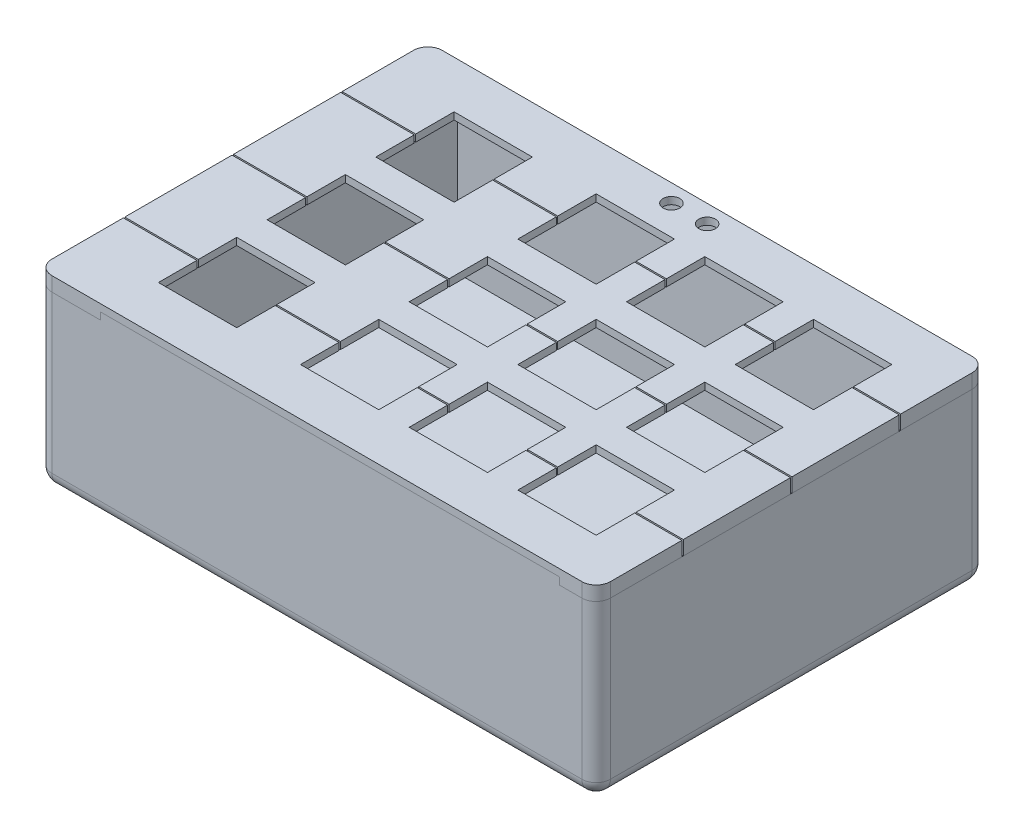
SolidWorks part; units mm, degrees
other "Lid4"
other "Lid2"
other "Lid3"
other "Lid1"
other "Base"
ref_plane "Front" through (0, 0, 0) normal (0, 0, 1) x (1, 0, 0)
ref_plane "Top" through (0, 0, 0) normal (0, 1, 0) x (1, 0, 0)
ref_plane "Right" through (0, 0, 0) normal (1, 0, 0) x (0, 0, -1)
sketch "Sketch1" plane through (0, 0, 0) normal (0, 1, 0) x (1, 0, 0)
  line L0 (2.6035, 12.3825) -> (8.0137, 12.3825) construction
  line L1 (-49.7332, -34.7472) -> (49.7332, -34.7472)
  line L2 (-49.7332, -34.7472) -> (-49.7332, 34.7472)
  line L3 (-49.7332, 34.7472) -> (49.7332, 34.7472)
  line L4 (49.7332, -34.7472) -> (49.7332, 34.7472)
  line L5 (-49.7332, -34.7472) -> (49.7332, 34.7472) construction
  line L6 (-49.7332, 34.7472) -> (49.7332, -34.7472) construction
  line L7 (-11.3411, 26.3271) -> (2.6035, 26.3271)
  line L8 (-11.3411, 26.3271) -> (-11.3411, 12.3825)
  line L9 (-11.3411, 12.3825) -> (2.6035, 12.3825)
  line L10 (2.6035, 26.3271) -> (2.6035, 12.3825)
  line L11 (8.0137, 26.3271) -> (21.9583, 26.3271)
  line L12 (8.0137, 26.3271) -> (8.0137, 12.3825)
  line L13 (8.0137, 12.3825) -> (21.9583, 12.3825)
  line L14 (21.9583, 26.3271) -> (21.9583, 12.3825)
  line L15 (27.3685, 26.3271) -> (41.3131, 26.3271)
  line L16 (27.3685, 26.3271) -> (27.3685, 12.3825)
  line L17 (27.3685, 12.3825) -> (41.3131, 12.3825)
  line L18 (41.3131, 26.3271) -> (41.3131, 12.3825)
  line L19 (21.9583, 12.3825) -> (27.3685, 12.3825) construction
  line L20 (2.6035, 12.3825) -> (2.6035, 6.9723) construction
  line L21 (-11.3411, 6.9723) -> (2.6035, 6.9723)
  line L22 (-11.3411, 6.9723) -> (-11.3411, -6.9723)
  line L23 (-11.3411, -6.9723) -> (2.6035, -6.9723)
  line L24 (2.6035, 6.9723) -> (2.6035, -6.9723)
  line L25 (8.0137, 6.9723) -> (21.9583, 6.9723)
  line L26 (8.0137, 6.9723) -> (8.0137, -6.9723)
  line L27 (8.0137, -6.9723) -> (21.9583, -6.9723)
  line L28 (21.9583, 6.9723) -> (21.9583, -6.9723)
  line L29 (27.3685, 6.9723) -> (41.3131, 6.9723)
  line L30 (27.3685, 6.9723) -> (27.3685, -6.9723)
  line L31 (27.3685, -6.9723) -> (41.3131, -6.9723)
  line L32 (41.3131, 6.9723) -> (41.3131, -6.9723)
  line L33 (21.9583, 12.3825) -> (21.9583, 6.9723) construction
  line L34 (41.3131, 12.3825) -> (41.3131, 6.9723) construction
  line L35 (2.6035, -12.3825) -> (2.6035, -6.9723) construction
  line L36 (-11.3411, -12.3825) -> (2.6035, -12.3825)
  line L37 (-11.3411, -12.3825) -> (-11.3411, -26.3271)
  line L38 (-11.3411, -26.3271) -> (2.6035, -26.3271)
  line L39 (2.6035, -12.3825) -> (2.6035, -26.3271)
  line L40 (8.0137, -12.3825) -> (21.9583, -12.3825)
  line L41 (8.0137, -12.3825) -> (8.0137, -26.3271)
  line L42 (8.0137, -26.3271) -> (21.9583, -26.3271)
  line L43 (21.9583, -12.3825) -> (21.9583, -26.3271)
  line L44 (27.3685, -12.3825) -> (41.3131, -12.3825)
  line L45 (27.3685, -12.3825) -> (27.3685, -26.3271)
  line L46 (27.3685, -26.3271) -> (41.3131, -26.3271)
  line L47 (41.3131, -12.3825) -> (41.3131, -26.3271)
  line L48 (21.9583, -12.3825) -> (21.9583, -6.9723) construction
  line L49 (41.3131, -6.9723) -> (41.3131, -12.3825) construction
  line L50 (41.3131, -26.3271) -> (49.7332, -26.3271) construction
  line L51 (-13.4112, 10.3124) -> (4.6736, 10.3124) construction
  line L52 (-13.4112, 10.3124) -> (-13.4112, 28.3972) construction
  line L53 (-13.4112, 28.3972) -> (4.6736, 28.3972) construction
  line L54 (4.6736, 10.3124) -> (4.6736, 28.3972) construction
  line L55 (-13.4112, 10.3124) -> (4.6736, 28.3972) construction
  line L56 (-13.4112, 28.3972) -> (4.6736, 10.3124) construction
  line L57 (24.0284, 10.3124) -> (5.9436, 10.3124) construction
  line L58 (24.0284, 10.3124) -> (24.0284, 28.3972) construction
  line L59 (24.0284, 28.3972) -> (5.9436, 28.3972) construction
  line L60 (5.9436, 10.3124) -> (5.9436, 28.3972) construction
  line L61 (24.0284, 10.3124) -> (5.9436, 28.3972) construction
  line L62 (24.0284, 28.3972) -> (5.9436, 10.3124) construction
  line L63 (41.3131, -26.3271) -> (41.3131, -34.7472) construction
  line L64 (34.3408, 26.3271) -> (34.3408, 19.3548) construction
  line L65 (-36.6395, 12.3825) -> (-22.6949, 12.3825)
  line L66 (-36.6395, 12.3825) -> (-36.6395, 26.3271)
  line L67 (-36.6395, 26.3271) -> (-22.6949, 26.3271)
  line L68 (-22.6949, 12.3825) -> (-22.6949, 26.3271)
  line L69 (-36.6395, 12.3825) -> (-22.6949, 26.3271) construction
  line L70 (-36.6395, 26.3271) -> (-22.6949, 12.3825) construction
  line L71 (-36.6395, -6.9723) -> (-22.6949, -6.9723)
  line L72 (-36.6395, -6.9723) -> (-36.6395, 6.9723)
  line L73 (-36.6395, 6.9723) -> (-22.6949, 6.9723)
  line L74 (-22.6949, -6.9723) -> (-22.6949, 6.9723)
  line L75 (-36.6395, -6.9723) -> (-22.6949, 6.9723) construction
  line L76 (-36.6395, 6.9723) -> (-22.6949, -6.9723) construction
  line L77 (-36.6395, -26.3271) -> (-22.6949, -26.3271)
  line L78 (-36.6395, -26.3271) -> (-36.6395, -12.3825)
  line L79 (-36.6395, -12.3825) -> (-22.6949, -12.3825)
  line L80 (-22.6949, -26.3271) -> (-22.6949, -12.3825)
  line L81 (-36.6395, -26.3271) -> (-22.6949, -12.3825) construction
  line L82 (-36.6395, -12.3825) -> (-22.6949, -26.3271) construction
  line L83 (-43.3832, 28.3591) -> (-15.9512, 28.3591) construction
  line L84 (-43.3832, 28.3591) -> (-43.3832, 10.3505) construction
  line L85 (-43.3832, 10.3505) -> (-15.9512, 10.3505) construction
  line L86 (-15.9512, 28.3591) -> (-15.9512, 10.3505) construction
  line L87 (-43.3832, 28.3591) -> (-15.9512, 10.3505) construction
  line L88 (-43.3832, 10.3505) -> (-15.9512, 28.3591) construction
  line L89 (-43.3832, 9.0043) -> (-15.9512, 9.0043) construction
  line L90 (-43.3832, 9.0043) -> (-43.3832, -9.0043) construction
  line L91 (-43.3832, -9.0043) -> (-15.9512, -9.0043) construction
  line L92 (-15.9512, 9.0043) -> (-15.9512, -9.0043) construction
  line L93 (-43.3832, 9.0043) -> (-15.9512, -9.0043) construction
  line L94 (-43.3832, -9.0043) -> (-15.9512, 9.0043) construction
  line L95 (-43.3832, -10.3505) -> (-15.9512, -10.3505)
  line L96 (-43.3832, -10.3505) -> (-43.3832, -28.3591) construction
  line L97 (-43.3832, -28.3591) -> (-15.9512, -28.3591) construction
  line L98 (-15.9512, -10.3505) -> (-15.9512, -28.3591) construction
  line L99 (-43.3832, -10.3505) -> (-15.9512, -28.3591) construction
  line L100 (-43.3832, -28.3591) -> (-15.9512, -10.3505) construction
  line L101 (25.2984, 10.3124) -> (43.3832, 10.3124) construction
  line L102 (25.2984, 10.3124) -> (25.2984, 28.3972) construction
  line L103 (25.2984, 28.3972) -> (43.3832, 28.3972) construction
  line L104 (43.3832, 10.3124) -> (43.3832, 28.3972) construction
  line L105 (25.2984, 10.3124) -> (43.3832, 28.3972) construction
  line L106 (25.2984, 28.3972) -> (43.3832, 10.3124) construction
  point P0 (0, 0)
  point P42 (14.986, 19.3548)
  point P43 (-4.3688, 19.3548)
  point P49 (-4.3688, 26.3271)
  point P51 (-11.3411, 19.3548)
  point P54 (-29.6672, 19.3548)
  point P55 (14.986, 26.3271)
  point P57 (8.0137, 19.3548)
  point P63 (-29.6672, 0)
  point P68 (-29.6672, -19.3548)
  point P73 (-29.6672, 0)
  point P75 (-29.6672, 19.3548)
  point P83 (-29.6672, -19.3548)
  point P89 (34.3408, 19.3548)
  dimension "D1" = 69.4944
  dimension "D2" = 6.35
  dimension "D3" = 13.9446
  dimension "D4" = 18.0848
  dimension "D5" = 1.27
  dimension "D6" = 6.35
  dimension "D7" = 18.0086
  dimension "D8" = 27.432
  dimension "D9" = 2.54
extrude "Boss-Extrude1" add sketch "Sketch1" along normal blind 1.27 contours L1 L4 L3 L2 L80 L77 L78 L79 L74 L71 L72 L73 L68 L65 L66 L67 L7 L10 L9 L8 L11 L14 L13 L12 L15 L18 L17 L16 L21 L24 L23 L22 L25 L28 L27 L26 L29 L32 L31 region at (-48.5198, 0, 0)
sketch "Sketch2" plane through (0, 1.27, 0) normal (0, 1, 0) x (1, 0, 0)
  line L0 (-49.7332, 19.3548) -> (49.7332, 19.3548)
  line L1 (-49.7332, -34.7472) -> (-49.7332, 34.7472) construction
  line L2 (49.7332, -34.7472) -> (49.7332, 34.7472) construction
  line L3 (27.3685, 26.3271) -> (27.3685, 12.3825) construction
  line L4 (-49.7332, 0) -> (49.7332, 0)
  line L5 (41.3131, 6.9723) -> (41.3131, -6.9723) construction
  line L6 (41.3131, -12.3825) -> (41.3131, -26.3271) construction
  line L7 (-49.7332, -19.3548) -> (49.7332, -19.3548)
  point P8 (27.3685, 19.3548)
  point P15 (41.3131, 0)
  point P18 (41.3131, -19.3548)
sketch "Sketch4" plane through (0, 1.27, 0) normal (0, 1, 0) x (1, 0, 0)
  line L0 (-49.7332, 19.3548) -> (49.7332, 19.3548) construction
  line L1 (-49.7332, 0) -> (49.7332, 0) construction
  line L2 (-49.7332, -19.3548) -> (49.7332, -19.3548) construction
  line L3 (2.6035, 26.3271) -> (8.0137, 26.3271) construction
  line L4 (21.9583, 26.3271) -> (27.3685, 26.3271) construction
  line L5 (-22.6949, 26.3271) -> (-11.3411, 26.3271) construction
  line L6 (41.3131, 26.3271) -> (49.7332, 26.3271) construction
  line L7 (49.7332, -34.7472) -> (49.7332, 34.7472) construction
  line L8 (-36.6395, 26.3271) -> (-49.7332, 26.3271) construction
  line L9 (-49.7332, -34.7472) -> (-49.7332, 34.7472) construction
  point P0 (-17.018, 19.3548)
  point P1 (-17.018, 0)
  point P4 (-17.018, -19.3548)
  point P7 (5.3086, -19.3548)
  point P10 (5.3086, 0)
  point P11 (5.3086, 19.3548)
  point P12 (24.6634, 19.3548)
  point P13 (24.6634, 0)
  point P14 (24.6634, -19.3548)
  point P15 (45.5232, 19.3548)
  point P16 (45.5232, 0)
  point P17 (45.5232, -19.3548)
  point P18 (-43.1864, 19.3548)
  point P19 (-43.1864, 0)
  point P20 (-43.1864, -19.3548)
  point P43 (5.3086, 26.3271)
  point P44 (24.6634, 26.3271)
  point P45 (-43.1864, 26.3271)
  point P46 (-17.018, 26.3271)
  point P47 (45.5232, 26.3271)
sketch "Sketch6" plane through (0, 0, 0) normal (0, -1, 0) x (1, 0, 0)
  line L0 (-49.7332, -34.7472) -> (49.7332, -34.7472) construction
  line L1 (-49.7332, 34.7472) -> (-38.5445, 34.7472)
  line L2 (-49.7332, 34.7472) -> (-49.7332, -34.7472)
  line L3 (-49.7332, -34.7472) -> (-38.5445, -34.7472)
  line L4 (-38.5445, 34.7472) -> (-38.5445, -34.7472)
  line L5 (-49.7332, 34.7472) -> (49.7332, 34.7472) construction
  line L6 (43.2181, 34.7472) -> (49.7332, 34.7472)
  line L7 (43.2181, 34.7472) -> (43.2181, -34.7472)
  line L8 (43.2181, -34.7472) -> (49.7332, -34.7472)
  line L9 (49.7332, 34.7472) -> (49.7332, -34.7472)
  line L12 (-36.6395, 26.3271) -> (-36.6395, 12.3825) construction
  line L13 (41.3131, 12.3825) -> (41.3131, 26.3271) construction
  dimension "D1" = 1.905
  dimension "D2" = 1.905
extrude "Boss-Extrude2" add sketch "Sketch6" along normal blind 1.27
extrude "Cut-Extrude-Thin2" cut sketch "Sketch2" against normal through all thin thin type mid plane wall 0.254
sketch "Sketch8" plane through (0, 1.27, 0) normal (0, 1, 0) x (1, 0, 0)
  line L0 (41.3131, -26.3271) -> (41.3131, -34.7472) construction
  line L1 (-49.7332, 19.4818) -> (-36.6395, 19.4818) construction
  line L2 (41.3131, 19.4818) -> (49.7332, 19.4818) construction
  line L3 (49.7332, -19.2278) -> (49.7332, -0.127) construction
  line L4 (49.7332, 0.127) -> (49.7332, 19.2278) construction
  line L5 (0, 0) -> (0, -9.9001) construction
  line L6 (-49.7332, -34.7472) -> (49.7332, -34.7472) construction
  line L7 (-9.6807, 0) -> (8.7732, 0) construction
  point P0 (-45.5232, 30.5371)
  point P1 (-43.1864, 9.6774)
  point P2 (-43.1864, -9.6774)
  point P3 (-45.5232, -30.5371)
  point P4 (45.5232, -30.5371)
  point P5 (45.5232, -9.6774)
  point P6 (45.5232, 9.6774)
  point P7 (45.5232, 30.5371)
  point P10 (-43.1864, 19.4818)
  point P13 (45.5232, 19.4818)
  point P16 (49.7332, -9.6774)
  point P19 (49.7332, 9.6774)
  point P22 (41.3131, -30.5371)
sketch "Sketch9" plane through (0, -1.27, 0) normal (0, -1, 0) x (1, 0, 0)
  line L3 (0, -34.7472) -> (0, 34.7472) construction
  line L6 (-43.2181, -27.1145) -> (-49.7332, -27.1145) construction
  line L9 (-43.2181, -9.6774) -> (-49.7332, -9.6774) construction
  line L12 (-43.2181, 9.6774) -> (-49.7332, 9.6774) construction
  line L15 (-43.2181, 27.1145) -> (-49.7332, 27.1145) construction
  line L18 (43.2181, 27.1145) -> (49.7332, 27.1145) construction
  line L19 (43.2181, 34.7472) -> (43.2181, 19.4818) construction
  line L20 (49.7332, 19.4818) -> (49.7332, 34.7472) construction
  line L21 (43.2181, 9.6774) -> (49.7332, 9.6774) construction
  line L22 (43.2181, 19.2278) -> (43.2181, 0.127) construction
  line L23 (49.7332, 0.127) -> (49.7332, 19.2278) construction
  line L24 (43.2181, -9.6774) -> (49.7332, -9.6774) construction
  line L25 (43.2181, -0.127) -> (43.2181, -19.2278) construction
  line L26 (49.7332, -19.2278) -> (49.7332, -0.127) construction
  line L27 (43.2181, -27.1145) -> (49.7332, -27.1145) construction
  line L28 (43.2181, -19.4818) -> (43.2181, -34.7472) construction
  line L29 (49.7332, -34.7472) -> (49.7332, -19.4818) construction
  line L30 (-38.5445, 34.7472) -> (43.2181, 34.7472) construction
  line L31 (-38.5445, -34.7472) -> (43.2181, -34.7472) construction
  circle A0 centre (-46.4757, -27.1145) radius 1.5875
  circle A1 centre (-46.4757, -9.6774) radius 1.5875
  circle A2 centre (-46.4757, 9.6774) radius 1.5875
  circle A3 centre (-46.4757, 27.1145) radius 1.5875
  circle A4 centre (46.4757, 27.1145) radius 1.5875
  circle A5 centre (46.4757, 9.6774) radius 1.5875
  circle A6 centre (46.4757, -9.6774) radius 1.5875
  circle A7 centre (46.4757, -27.1145) radius 1.5875
  point P22 (0, 0)
  point P25 (0, 0)
  dimension "D1" = 3.175
extrude "Boss-Extrude3" add sketch "Sketch9" along normal blind 6.35 draft 4
ref_plane "Plane1" through (0, -31.75, 0) normal (0, -1, 0) x (-1, 0, 0)
sketch "Sketch10" plane through (0, -31.75, 0) normal (0, -1, 0) x (-1, 0, 0)
  line L0 (49.7332, -34.7472) -> (-49.7332, -34.7472) construction
  line L1 (49.7332, 34.7472) -> (-49.7332, 34.7472) construction
  line L2 (49.7332, -34.7472) -> (-49.7332, -34.7472)
  line L3 (49.7332, 34.7472) -> (-49.7332, 34.7472)
  line L4 (-49.7332, 34.7472) -> (-49.7332, -34.7472)
  line L5 (49.7332, 34.7472) -> (49.7332, -34.7472)
extrude "Boss-Extrude4" add sketch "Sketch10" against normal blind 1.27 separate body
sketch "Sketch11" plane through (0, -30.48, 0) normal (0, 1, 0) x (1, 0, 0)
  line L0 (49.7332, -34.7472) -> (43.2181, -34.7472) construction
  line L1 (43.2181, 34.7472) -> (49.7332, 34.7472) construction
  line L2 (49.7332, -34.7472) -> (43.2181, -34.7472)
  line L3 (43.2181, 34.7472) -> (49.7332, 34.7472)
  line L4 (49.7332, -34.7472) -> (49.7332, 34.7472)
  line L5 (43.2181, -33.4772) -> (43.2181, 33.4772)
  line L6 (0, -34.7472) -> (0, 34.7472) construction
  line L7 (49.7332, -34.7472) -> (-49.7332, -34.7472) construction
  line L8 (-49.7332, 34.7472) -> (49.7332, 34.7472) construction
  line L9 (-43.2181, -33.4772) -> (-43.2181, 33.4772)
  line L10 (-49.7332, -34.7472) -> (-49.7332, 34.7472)
  line L11 (-43.2181, 34.7472) -> (-49.7332, 34.7472)
  line L12 (-49.7332, -34.7472) -> (-43.2181, -34.7472)
  line L13 (-43.2181, 33.4772) -> (43.2181, 33.4772)
  line L14 (-43.2181, 0) -> (43.2181, 0) construction
  line L15 (-49.7332, 34.7472) -> (49.7332, 34.7472) construction
  line L16 (-43.2181, -33.4772) -> (43.2181, -33.4772)
  line L18 (-43.2181, 34.7472) -> (43.2181, 34.7472)
  line L19 (-43.2181, -34.7472) -> (43.2181, -34.7472)
  point P23 (0, 0)
  point P24 (0, 0)
  dimension "D1" = 1.27
extrude "Boss-Extrude5" add sketch "Sketch11" along normal up to surface (29.21 mm away) up to face at (46.4757, -1.27, -28.702)
sketch "Sketch12" plane through (0, -1.27, 0) normal (0, 1, 0) x (1, 0, 0)
  line L1 (-38.5445, -19.4818) -> (-38.5445, -34.7472) construction
  line L2 (-38.5445, -33.4772) -> (-38.5445, -34.7472)
  line L3 (0, -33.4772) -> (0, 0) construction
  line L4 (43.2181, -33.4772) -> (-43.2181, -33.4772) construction
  line L6 (-38.5445, -33.4772) -> (43.2181, -33.4772)
  line L7 (-43.2181, -33.4772) -> (43.2181, -33.4772) construction
  line L8 (43.2181, -34.7472) -> (43.2181, -19.4818) construction
  line L9 (-7.2505, 0) -> (13.3194, 0) construction
  line L10 (-38.5445, 33.4772) -> (43.2181, 33.4772)
  line L11 (43.2181, 33.4772) -> (43.2181, 34.7472)
  line L12 (-38.5445, 33.4772) -> (-38.5445, 34.7472)
  line L13 (-38.5445, 34.7472) -> (43.2181, 34.7472)
  line L14 (-38.5445, -34.7472) -> (43.2181, -34.7472)
  line L17 (43.2181, -33.4772) -> (43.2181, -34.7472)
  line L18 (49.7332, -34.7472) -> (-49.7332, -34.7472) construction
  point P10 (40.8051, -33.4772)
  point P26 (0, 0)
  point P27 (40.4973, -34.7472)
extrude "Boss-Extrude6" add sketch "Sketch12" along normal up to surface (1.27 mm away) up to face at (3.6576, 0, 9.6774)
sketch "Sketch13" plane through (0, 1.27, 0) normal (0, 1, 0) x (1, 0, 0)
  line L0 (0, 34.7472) -> (0, 28.3972) construction
  line L3 (-49.7332, 31.5722) -> (49.7332, 31.5722) construction
  line L4 (-49.7332, -34.7472) -> (-49.7332, 34.7472) construction
  line L5 (49.7332, -34.7472) -> (49.7332, 34.7472) construction
  line L6 (-49.7332, 34.7472) -> (49.7332, 34.7472) construction
  line L7 (-13.4112, 28.3972) -> (4.6736, 28.3972) construction
  circle A0 centre (3.175, 31.5722) radius 1.4859
  circle A1 centre (-3.175, 31.5722) radius 1.4859
  point P12 (0, 31.5722)
  point P18 (0, 0)
  dimension "D1" = 2.9718
  dimension "D2" = 6.35
extrude "Cut-Extrude1" cut sketch "Sketch13" against normal up to next (1.27 mm away)
sketch "Sketch14" plane through (-49.7332, 0, 0) normal (-1, 0, 0) x (0, 0, 1)
  line L0 (-33.4772, -30.48) -> (33.4772, -30.48) construction
  line L1 (-33.4772, -30.48) -> (33.4772, -30.48) construction
  line L2 (0, 0) -> (0, -30.48) construction
  line L3 (-5.715, -22.86) -> (5.715, -22.86)
  line L4 (-5.715, -22.86) -> (-5.715, -30.48)
  line L5 (-5.715, -30.48) -> (5.715, -30.48)
  line L6 (5.715, -22.86) -> (5.715, -30.48)
  point P9 (0, 0)
  point P10 (0, 0)
  dimension "D1" = 7.62
  dimension "D2" = 11.43
extrude "Cut-Extrude3" cut sketch "Sketch14" against normal up to next (6.5151 mm away) contours L3 L6 L5 L4
sketch "Sketch16" plane through (0, -1.27, 0) normal (0, -1, 0) x (1, 0, 0)
  circle A0 centre (46.4757, 27.1145) radius 1.5875 construction
  circle A1 centre (46.4757, 9.6774) radius 1.5875 construction
  circle A2 centre (46.4757, -9.6774) radius 1.5875 construction
  circle A3 centre (46.4757, -27.1145) radius 1.5875 construction
  circle A4 centre (-46.4757, -27.1145) radius 1.5875 construction
  circle A5 centre (-46.4757, -9.6774) radius 1.5875 construction
  circle A6 centre (-46.4757, 9.6774) radius 1.5875 construction
  circle A7 centre (-46.4757, 27.1145) radius 1.5875 construction
  circle A72 centre (46.4757, 27.1145) radius 1.5875 construction
  circle A73 centre (46.4757, 9.6774) radius 1.5875 construction
  circle A74 centre (46.4757, -9.6774) radius 1.5875 construction
  circle A75 centre (46.4757, -27.1145) radius 1.5875 construction
  circle A76 centre (-46.4757, -27.1145) radius 1.5875 construction
  circle A77 centre (-46.4757, -9.6774) radius 1.5875 construction
  circle A78 centre (-46.4757, 9.6774) radius 1.5875 construction
  circle A79 centre (-46.4757, 27.1145) radius 1.5875 construction
  circle A80 centre (46.4757, 27.1145) radius 1.7145
  circle A81 centre (46.4757, 9.6774) radius 1.7145
  circle A82 centre (46.4757, -9.6774) radius 1.7145
  circle A83 centre (46.4757, -27.1145) radius 1.7145
  circle A84 centre (-46.4757, -27.1145) radius 1.7145
  circle A85 centre (-46.4757, -9.6774) radius 1.7145
  circle A86 centre (-46.4757, 9.6774) radius 1.7145
  circle A87 centre (-46.4757, 27.1145) radius 1.7145
  dimension "D1" = 0.127
extrude "Cut-Extrude5" cut sketch "Sketch16" along normal blind 6.604
chamfer "Chamfer1" distance 0.508 angle 45 8 edges at (-46.4757, -1.27, -28.829) (-46.4757, -1.27, -11.3919) (-46.4757, -1.27, 7.9629) (-46.4757, -1.27, 25.4) (46.4757, -1.27, -28.829) (46.4757, -1.27, -11.3919) (46.4757, -1.27, 7.9629) (46.4757, -1.27, 25.4)
fillet "Fillet1" radius 2.54 8 edges at (-49.7332, -31.75, 0) (0, -31.75, -34.7472) (0, -31.75, 34.7472) (49.7332, -31.75, 0) (49.7332, -16.51, 34.7472) (49.7332, -16.51, -34.7472) (-49.7332, -16.51, -34.7472) (-49.7332, -16.51, 34.7472)
fillet "Fillet2" radius 2.54 2 edges at (49.7332, 0, 34.7472) (-49.7332, 0, 34.7472)
fillet "Fillet3" radius 2.54 2 edges at (-49.7332, 0, -34.7472) (49.7332, 0, -34.7472)
